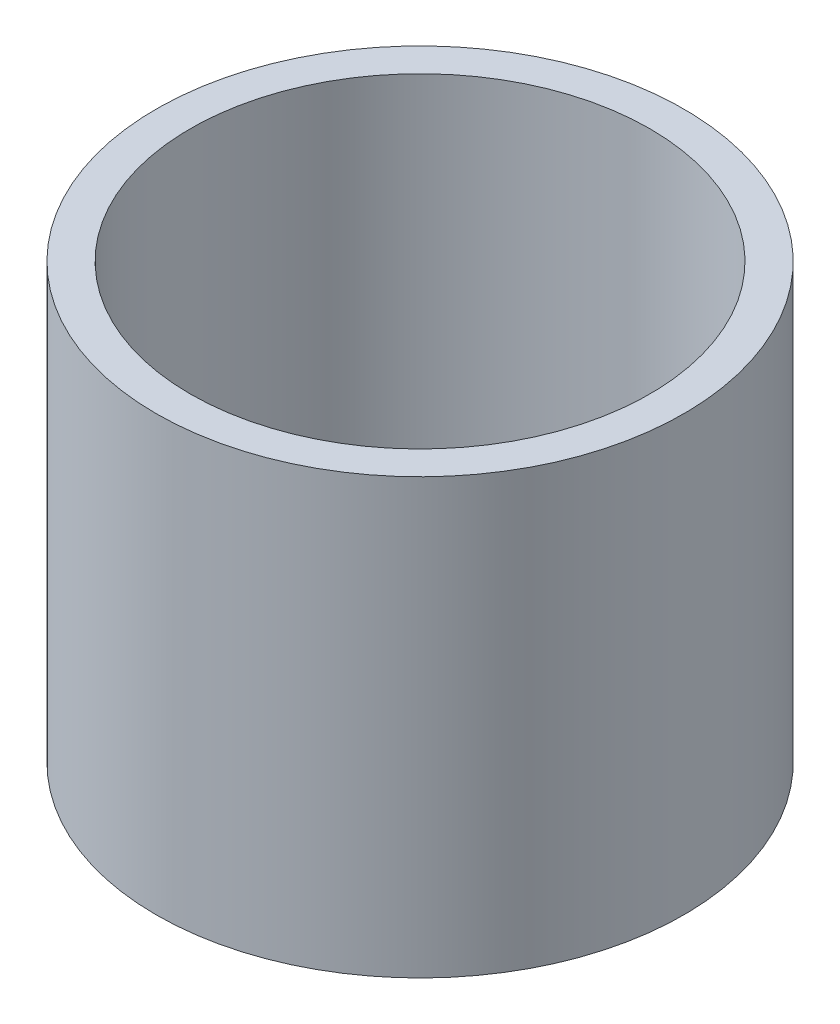
SolidWorks part; units mm, degrees
ref_plane "Ön Düzlem" through (0, 0, 0) normal (0, 0, 1) x (1, 0, 0)
ref_plane "Üst Düzlem" through (0, 0, 0) normal (0, 1, 0) x (1, 0, 0)
ref_plane "Sağ Düzlem" through (0, 0, 0) normal (1, 0, 0) x (0, 0, -1)
sketch "Sketch1" plane through (0, 0, 0) normal (0, 1, 0) x (1, 0, 0)
  circle A0 centre (0, 0) radius 135
  circle A1 centre (0, 0) radius 155
extrude "Boss-Extrude1" add sketch "Sketch1" along normal blind 255
